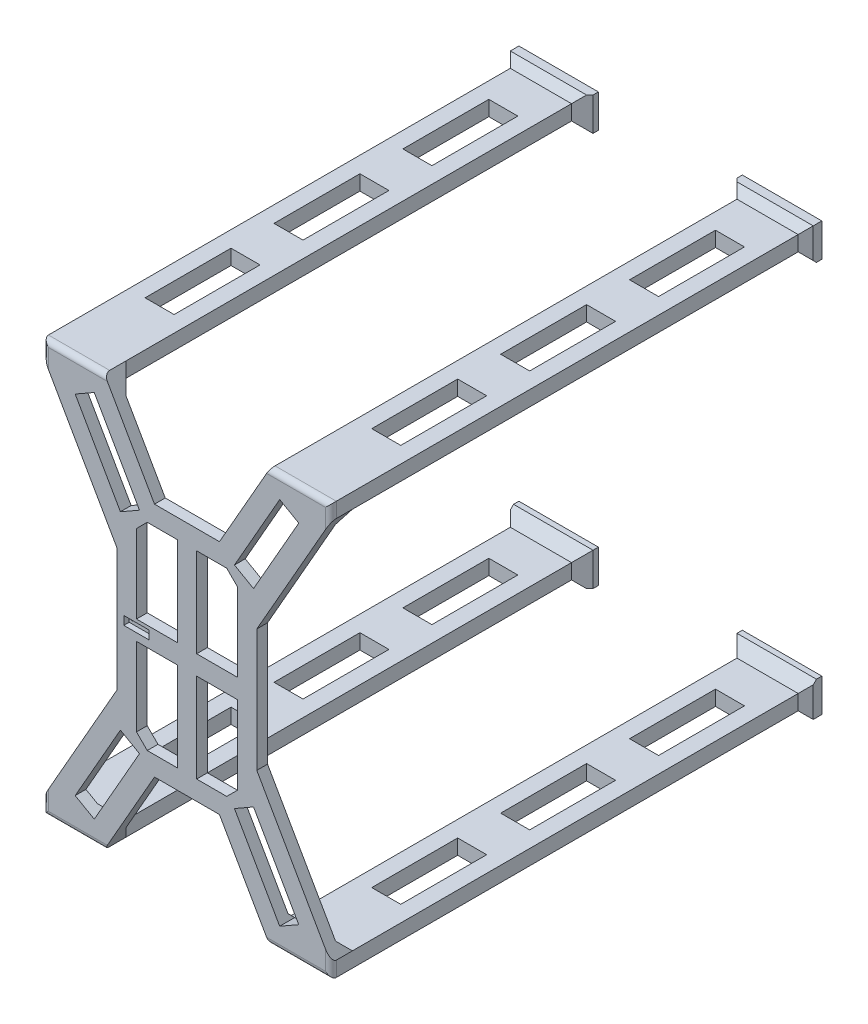
SolidWorks part; units mm, degrees
ref_plane "前视基准面" through (0, 0, 0) normal (0, 0, 1) x (1, 0, 0)
ref_plane "上视基准面" through (0, 0, 0) normal (0, 1, 0) x (1, 0, 0)
ref_plane "右视基准面" through (0, 0, 0) normal (1, 0, 0) x (0, 0, -1)
sketch "草图1" plane through (0, 0, 0) normal (0, 0, 1) x (1, 0, 0)
  line L0 (44, 200) -> (44, -200) construction
  line L1 (-325, -200) -> (325, -200) construction
  line L2 (-325, -200) -> (-325, 200) construction
  line L3 (-325, 200) -> (325, 200) construction
  line L4 (325, -200) -> (325, 200) construction
  line L5 (-325, -200) -> (325, 200) construction
  line L6 (-325, 200) -> (325, -200) construction
  line L7 (-290, 200) -> (-290, -200) construction
  line L8 (-325, 100) -> (325, 100) construction
  line L9 (-325, 0) -> (325, 0) construction
  line L10 (-325, -100) -> (325, -100) construction
  line L11 (-310, 200) -> (-310, -200) construction
  line L12 (-270, 200) -> (-270, -200) construction
  line L13 (24, 200) -> (24, -200) construction
  line L14 (64, 200) -> (64, -200) construction
  line L16 (-46, 192) -> (11, 192)
  line L17 (79, 0) -> (325, 0) construction
  line L18 (-46, 192) -> (-46, 178)
  line L19 (-46, 178) -> (11, 178)
  line L20 (11, 192) -> (11, 178)
  line L21 (-257, -178) -> (-200, -178)
  line L22 (-257, -178) -> (-257, -192)
  line L23 (325, 0) -> (225, 0) construction
  line L24 (-257, -192) -> (-200, -192)
  line L25 (-200, -178) -> (-200, -192)
  line L26 (-46, -178) -> (11, -178)
  line L27 (-46, -178) -> (-46, -192)
  line L28 (-46, -192) -> (11, -192)
  line L29 (11, -178) -> (11, -192)
  line L37 (-325, 185) -> (64, 185) construction
  line L38 (-325, -185) -> (64, -185) construction
  line L39 (-16, 200) -> (-16, 185) construction
  line L40 (4, 200) -> (4, 185) construction
  line L41 (-36, 200) -> (-36, 185) construction
  line L42 (-250, 200) -> (-250, 185) construction
  line L43 (-230, 200) -> (-230, 185) construction
  line L44 (-210, 200) -> (-210, 185) construction
  line L45 (-250, -200) -> (-250, -185) construction
  line L46 (-230, -200) -> (-230, -185) construction
  line L47 (-210, -200) -> (-210, -185) construction
  line L48 (4, -200) -> (4, -185) construction
  line L49 (-16, -200) -> (-16, -185) construction
  line L50 (-36, -200) -> (-36, -185) construction
  line L51 (64, -185) -> (325, -185) construction
  line L64 (-257, 192) -> (-200, 192)
  line L65 (-257, 192) -> (-257, 178)
  line L66 (-257, 178) -> (-200, 178)
  line L67 (-200, 192) -> (-200, 178)
  circle A0 centre (-310, 100) radius 3
  circle A1 centre (-290, 100) radius 3
  circle A2 centre (-270, 100) radius 3
  circle A3 centre (-310, 0) radius 3
  circle A4 centre (-290, 0) radius 3
  circle A5 centre (-270, 0) radius 3
  circle A6 centre (-310, -100) radius 3
  circle A7 centre (-290, -100) radius 3
  circle A8 centre (-270, -100) radius 3
  circle A9 centre (24, 100) radius 3
  circle A10 centre (44, 100) radius 3
  circle A11 centre (64, 100) radius 3
  circle A12 centre (24, -100) radius 3
  circle A13 centre (44, -100) radius 3
  circle A14 centre (64, -100) radius 3
  circle A15 centre (24, 0) radius 3
  circle A16 centre (44, 0) radius 3
  circle A17 centre (64, 0) radius 3
  circle A44 centre (-310, -185) radius 3
  circle A45 centre (-290, -185) radius 3
  circle A46 centre (-270, -185) radius 3
  circle A47 centre (24, -185) radius 3
  circle A48 centre (44, -185) radius 3
  circle A49 centre (64, -185) radius 3
  circle A50 centre (-310, 185) radius 3
  circle A51 centre (-290, 185) radius 3
  circle A52 centre (-270, 185) radius 3
  circle A53 centre (24, 185) radius 3
  circle A54 centre (44, 185) radius 3
  circle A55 centre (64, 185) radius 3
  circle A56 centre (-36, 185) radius 2
  circle A57 centre (-16, 185) radius 2
  circle A58 centre (4, 185) radius 2
  circle A59 centre (-250, 185) radius 2
  circle A60 centre (-230, 185) radius 2
  circle A61 centre (-210, 185) radius 2
  circle A62 centre (-250, -185) radius 2
  circle A63 centre (-230, -185) radius 2
  circle A64 centre (-210, -185) radius 2
  circle A65 centre (4, -185) radius 2
  circle A66 centre (-16, -185) radius 2
  circle A67 centre (-36, -185) radius 2
  point P0 (0, 0)
  dimension "D11" = 6
  dimension "D12" = 6
  dimension "D13" = 6
  dimension "D14" = 6
  dimension "D15" = 6
  dimension "D16" = 6
  dimension "D17" = 6
  dimension "D18" = 6
  dimension "D19" = 6
  dimension "D20" = 6
  dimension "D21" = 6
  dimension "D22" = 6
  dimension "D23" = 6
  dimension "D24" = 6
  dimension "D25" = 6
  dimension "D26" = 6
  dimension "D27" = 6
  dimension "D28" = 6
  dimension "D34" = 7
  dimension "D35" = 10
  dimension "D36" = 7
  dimension "D37" = 7
  dimension "D38" = 7
  dimension "D39" = 7
  dimension "D44" = 7
  dimension "D79" = 6
  dimension "D80" = 6
  dimension "D81" = 6
  dimension "D82" = 6
  dimension "D83" = 6
  dimension "D84" = 6
  dimension "D85" = 6
  dimension "D86" = 6
  dimension "D87" = 6
  dimension "D88" = 6
  dimension "D94" = 4
  dimension "D95" = 4
  dimension "D96" = 4
  dimension "D100" = 4
  dimension "D101" = 4
  dimension "D102" = 4
  dimension "D106" = 4
  dimension "D107" = 4
  dimension "D108" = 4
  dimension "D112" = 4
  dimension "D113" = 4
  dimension "D114" = 4
  dimension "D29" = 6
  dimension "D30" = 6
  dimension "D1" = 400
  dimension "D2" = 650
  dimension "D3" = 20
  dimension "D4" = 20
  dimension "D5" = 294
  dimension "D6" = 20
  dimension "D7" = 20
  dimension "D8" = 15
  dimension "D9" = 100
  dimension "D10" = 100
  dimension "D31" = 7
  dimension "D32" = 7
  dimension "D33" = 7
  dimension "D40" = 10
  dimension "D41" = 7
  dimension "D42" = 7
  dimension "D43" = 10
  dimension "D77" = 15
  dimension "D78" = 15
  dimension "D91" = 20
  dimension "D92" = 20
  dimension "D93" = 20
  dimension "D97" = 20
  dimension "D98" = 20
  dimension "D99" = 20
  dimension "D103" = 20
  dimension "D104" = 20
  dimension "D105" = 20
  dimension "D109" = 20
  dimension "D110" = 20
  dimension "D111" = 20
  dimension "D131" = 7
  dimension "D132" = 10
extrude "凸台-拉伸1" add sketch "草图1" along normal blind 440 contours L22 L21 L25 L24 | L27 L26 L29 L28 | L18 L16 L20 L19 | L65 L64 L67 L66
sketch "草图2" plane through (0, 0, 440) normal (0, 0, 1) x (1, 0, 0)
  line L0 (-257, 178) -> (-46, -192)
  line L1 (-200, 192) -> (11, -178)
  line L2 (-46, 192) -> (-257, -178)
  line L3 (-257, -178) -> (-257, -192) construction
  line L4 (-257, -178) -> (-200, -178) construction
  line L5 (11, 178) -> (-200, -192)
  line L6 (-257, 178) -> (-257, 192)
  line L7 (-257, 192) -> (-257, 178) construction
  line L8 (-257, 192) -> (-200, 192)
  line L9 (-46, 192) -> (11, 192)
  line L10 (11, 192) -> (11, 178)
  line L11 (-257, -178) -> (-257, -192)
  line L12 (-257, -192) -> (-200, -192)
  line L13 (-46, -192) -> (11, -192)
  line L14 (11, -192) -> (11, -178)
  line M2 (-200, -192) -> (-200, -178)
  line M3 (-200, -178) -> (-257, -178)
extrude "凸台-拉伸2" add sketch "草图2" along normal blind 10 contours L5 L0 L2 M3 M2 | L13 L14 L1 L5 L0 | L10 L9 L2 L1 L5 | L8 L6 L0 L2 L1 | L5 L1 L2 L0 | L12 L5 L10 L9 L2 L11 region at (-186.9015, 109.0049, 440) region at (-123, 0, 440) region at (-183.5044, -102.7988, 440) region at (-59.0985, -109.0049, 440) region at (-59.0985, 109.0049, 440)
sketch "草图4" plane through (0, 0, 0) normal (0, 0, -1) x (-1, 0, 0)
  line L0 (200, -185) -> (257, -185) construction
  line L1 (200, -178) -> (200, -192) construction
  line L2 (257, -178) -> (257, -192) construction
  line L5 (257, -192) -> (200, -192) construction
  line L6 (-11, -185) -> (46, -185) construction
  line L13 (211.5877, -182.25) -> (208.4123, -182.25)
  line L14 (208.4123, -182.25) -> (206.8246, -185)
  line L15 (206.8246, -185) -> (208.4123, -187.75)
  line L16 (208.4123, -187.75) -> (211.5877, -187.75)
  line L17 (211.5877, -187.75) -> (213.1754, -185)
  line L18 (213.1754, -185) -> (211.5877, -182.25)
  line L19 (251.5877, -182.25) -> (248.4123, -182.25)
  line L20 (248.4123, -182.25) -> (246.8246, -185)
  line L21 (246.8246, -185) -> (248.4123, -187.75)
  line L22 (248.4123, -187.75) -> (251.5877, -187.75)
  line L23 (251.5877, -187.75) -> (253.1754, -185)
  line L24 (253.1754, -185) -> (251.5877, -182.25)
  line L25 (-11, -178) -> (-11, -192) construction
  line L26 (46, -178) -> (46, -192) construction
  line L29 (46, -192) -> (-11, -192) construction
  line L30 (-11, 185) -> (46, 185) construction
  line L31 (-2.4123, -182.25) -> (-5.5877, -182.25)
  line L32 (-5.5877, -182.25) -> (-7.1754, -185)
  line L33 (-7.1754, -185) -> (-5.5877, -187.75)
  line L34 (-5.5877, -187.75) -> (-2.4123, -187.75)
  line L35 (-2.4123, -187.75) -> (-0.8246, -185)
  line L36 (-0.8246, -185) -> (-2.4123, -182.25)
  line L43 (37.5877, -187.75) -> (39.1754, -185)
  line L44 (39.1754, -185) -> (37.5877, -182.25)
  line L45 (37.5877, -182.25) -> (34.4123, -182.25)
  line L46 (34.4123, -182.25) -> (32.8246, -185)
  line L47 (32.8246, -185) -> (34.4123, -187.75)
  line L48 (34.4123, -187.75) -> (37.5877, -187.75)
  line L49 (-11, 192) -> (-11, 178) construction
  line L50 (46, 192) -> (46, 178) construction
  line L52 (46, 192) -> (-11, 192) construction
  line L55 (-2.4123, 187.75) -> (-5.5877, 187.75)
  line L56 (-5.5877, 187.75) -> (-7.1754, 185)
  line L57 (-7.1754, 185) -> (-5.5877, 182.25)
  line L58 (-5.5877, 182.25) -> (-2.4123, 182.25)
  line L59 (-2.4123, 182.25) -> (-0.8246, 185)
  line L60 (-0.8246, 185) -> (-2.4123, 187.75)
  line L67 (37.5877, 187.75) -> (34.4123, 187.75)
  line L68 (34.4123, 187.75) -> (32.8246, 185)
  line L69 (32.8246, 185) -> (34.4123, 182.25)
  line L70 (34.4123, 182.25) -> (37.5877, 182.25)
  line L71 (37.5877, 182.25) -> (39.1754, 185)
  line L72 (39.1754, 185) -> (37.5877, 187.75)
  line L73 (200, 185) -> (257, 185) construction
  line L74 (200, 192) -> (200, 178) construction
  line L75 (257, 192) -> (257, 178) construction
  line L77 (257, 192) -> (200, 192) construction
  line L79 (46, -178) -> (-11, -178) construction
  line L80 (211.5877, 187.75) -> (208.4123, 187.75)
  line L81 (208.4123, 187.75) -> (206.8246, 185)
  line L82 (206.8246, 185) -> (208.4123, 182.25)
  line L83 (208.4123, 182.25) -> (211.5877, 182.25)
  line L84 (211.5877, 182.25) -> (213.1754, 185)
  line L85 (213.1754, 185) -> (211.5877, 187.75)
  line L92 (251.5877, 187.75) -> (248.4123, 187.75)
  line L93 (248.4123, 187.75) -> (246.8246, 185)
  line L94 (246.8246, 185) -> (248.4123, 182.25)
  line L95 (248.4123, 182.25) -> (251.5877, 182.25)
  line L96 (251.5877, 182.25) -> (253.1754, 185)
  line L97 (253.1754, 185) -> (251.5877, 187.75)
  circle A1 centre (210, -185) radius 2.75 construction
  circle A2 centre (250, -185) radius 2.75 construction
  circle A3 centre (-4, -185) radius 2.75 construction
  circle A5 centre (36, -185) radius 2.75 construction
  circle A6 centre (-4, 185) radius 2.75 construction
  circle A8 centre (36, 185) radius 2.75 construction
  circle A9 centre (210, 185) radius 2.75 construction
  circle A10 centre (230, 185) radius 1.5
  circle A11 centre (250, 185) radius 2.75 construction
  circle A12 centre (16, 185) radius 1.5
  circle A13 centre (230, -185) radius 1.5
  circle A14 centre (16, -185) radius 1.5
  dimension "D14" = 20
  dimension "D19" = 3
  dimension "D4" = 7
  dimension "D9" = 20
  dimension "D11" = 3
  dimension "D25" = 3
  dimension "D26" = 3
  dimension "D3" = 5.5
  dimension "D5" = 5.5
  dimension "D6" = 7
  dimension "D7" = 20
  dimension "D8" = 5.5
  dimension "D10" = 5.5
  dimension "D12" = 7
  dimension "D13" = 5.5
  dimension "D15" = 5.5
  dimension "D16" = 7
  dimension "D17" = 20
  dimension "D18" = 5.5
  dimension "D20" = 5.5
  dimension "D21" = 20
  dimension "D22" = 20
  dimension "D23" = 20
  dimension "D24" = 20
extrude "切除-拉伸1" cut sketch "草图4" against normal blind 10
ref_plane "基准面1" through (-123, 0, 0) normal (-1, 0, 0) x (0, 0, 1)
ref_plane "基准面2" through (0, 0, 0) normal (0, -1, 0) x (-1, 0, 0)
sketch "草图6" plane through (0, 0, 440) normal (0, 0, -1) x (-1, 0, 0)
  line L0 (123, -204.7812) -> (123, 204.7812) construction
  line L1 (58, 110) -> (188, 110)
  line L2 (58, 110) -> (58, -110)
  line L3 (58, -110) -> (188, -110)
  line L4 (188, 110) -> (188, -110)
  line L5 (-145.6992, 0) -> (145.6992, 0) construction
  dimension "D1" = 65
  dimension "D2" = 65
  dimension "D3" = 110
  dimension "D4" = 110
extrude "凸台-拉伸3" add sketch "草图6" against normal up to surface (10 mm away) up to face at (-123, 0, 450)
sketch "草图7" plane through (0, 0, 450) normal (0, 0, 1) x (1, 0, 0)
  line L0 (-58, 57.0047) -> (-58, -57.0047) construction
  line L1 (-114, 9) -> (-76, 9)
  line L2 (-114, 9) -> (-114, 92)
  line L3 (-114, 92) -> (-76, 92)
  line L4 (-76, 9) -> (-76, 92)
  line L5 (-153.2378, 110) -> (-92.7622, 110) construction
  line L6 (-123, 204.7812) -> (-123, -204.7812) construction
  line L7 (-145.6992, 0) -> (145.6992, 0) construction
  line L8 (-92.7622, -110) -> (-153.2378, -110) construction
  line L9 (-114, -9) -> (-76, -9)
  line L10 (-114, -9) -> (-114, -92)
  line L11 (-114, -92) -> (-76, -92)
  line L12 (-76, -9) -> (-76, -92)
  line L13 (-132, 92) -> (-170, 92)
  line L14 (-132, 92) -> (-132, 9)
  line L15 (-132, 9) -> (-170, 9)
  line L16 (-170, 92) -> (-170, 9)
  line L17 (-132, -92) -> (-170, -92)
  line L18 (-132, -92) -> (-132, -9)
  line L19 (-132, -9) -> (-170, -9)
  line L20 (-170, -92) -> (-170, -9)
  line L21 (-188, -57.0047) -> (-188, 57.0047) construction
  line L22 (-227.0801, 161.8695) -> (-184.9728, 88.0321)
  line L23 (-184.9728, 88.0321) -> (-167.2085, 98.1625)
  line L24 (-167.2085, 98.1625) -> (-209.3158, 172)
  line L25 (-209.3158, 172) -> (-227.0801, 161.8695)
  line L26 (-257, 178) -> (-188, 57.0047) construction
  line L27 (-200, 192) -> (-153.2378, 110) construction
  line L28 (-78.7915, -98.1625) -> (-36.6842, -172)
  line L29 (-257, 192) -> (-200, 192) construction
  line L30 (-36.6842, 172) -> (-78.7915, 98.1625)
  line L31 (-78.7915, 98.1625) -> (-61.0272, 88.0321)
  line L32 (-61.0272, 88.0321) -> (-18.9199, 161.8695)
  line L33 (-18.9199, 161.8695) -> (-36.6842, 172)
  line L34 (11, 178) -> (-58, 57.0047) construction
  line L35 (-46, 192) -> (-92.7622, 110) construction
  line L36 (-46, 192) -> (11, 192) construction
  line L37 (-184.9728, -88.0321) -> (-227.0801, -161.8695)
  line L38 (-227.0801, -161.8695) -> (-209.3158, -172)
  line L39 (-209.3158, -172) -> (-167.2085, -98.1625)
  line L40 (-167.2085, -98.1625) -> (-184.9728, -88.0321)
  line L41 (-188, -57.0047) -> (-257, -178) construction
  line L42 (-153.2378, -110) -> (-200, -192) construction
  line L43 (-257, -192) -> (-200, -192) construction
  line L44 (-36.6842, -172) -> (-18.9199, -161.8695)
  line L45 (-18.9199, -161.8695) -> (-61.0272, -88.0321)
  line L46 (-61.0272, -88.0321) -> (-78.7915, -98.1625)
  line L47 (-58, -57.0047) -> (11, -178) construction
  line L48 (-92.7622, -110) -> (-46, -192) construction
  line L49 (-46, -192) -> (11, -192) construction
  dimension "D1" = 18
  dimension "D2" = 18
  dimension "D3" = 9
  dimension "D4" = 9
  dimension "D5" = 18
  dimension "D6" = 9
  dimension "D7" = 9
  dimension "D8" = 18
  dimension "D9" = 18
  dimension "D10" = 18
  dimension "D11" = 18
  dimension "D12" = 18
  dimension "D13" = 9
  dimension "D14" = 9
  dimension "D15" = 9
  dimension "D16" = 9
  dimension "D17" = 18
  dimension "D18" = 18
  dimension "D19" = 20
  dimension "D20" = 85
  dimension "D21" = 18
  dimension "D22" = 18
  dimension "D23" = 20
  dimension "D24" = 85
  dimension "D25" = 18
  dimension "D26" = 18
  dimension "D27" = 20
  dimension "D28" = 85
  dimension "D29" = 18
  dimension "D30" = 18
  dimension "D31" = 20
  dimension "D32" = 85
extrude "切除-拉伸2" cut sketch "草图7" against normal up to next (10 mm away)
sketch "草图8" plane through (0, -192, 0) normal (0, -1, 0) x (1, 0, 0)
  line L0 (-228.5, 0) -> (-228.5, 440) construction
  line L1 (-257, 0) -> (-200, 0) construction
  line L2 (-257, 440) -> (-200, 440) construction
  line L3 (-17.5, 0) -> (-17.5, 440) construction
  line L4 (-46, 0) -> (11, 0) construction
  line L5 (-257, 440) -> (-257, 0) construction
  line L6 (-242, 370) -> (-215, 370)
  line L7 (-242, 370) -> (-242, 290)
  line L8 (-242, 290) -> (-215, 290)
  line L9 (-215, 370) -> (-215, 290)
  line L10 (-242, 370) -> (-215, 290) construction
  line L11 (-242, 290) -> (-215, 370) construction
  line L12 (-242, 250) -> (-215, 250)
  line L13 (-242, 250) -> (-242, 170)
  line L14 (-242, 170) -> (-215, 170)
  line L15 (-215, 250) -> (-215, 170)
  line L16 (-242, 250) -> (-215, 170) construction
  line L17 (-242, 170) -> (-215, 250) construction
  line L18 (-242, 130) -> (-215, 130)
  line L19 (-242, 130) -> (-242, 50)
  line L20 (-242, 50) -> (-215, 50)
  line L21 (-215, 130) -> (-215, 50)
  line L22 (-242, 130) -> (-215, 50) construction
  line L23 (-242, 50) -> (-215, 130) construction
  line L24 (-46, 440) -> (-46, 0) construction
  line L25 (-31, 370) -> (-4, 370)
  line L26 (-31, 370) -> (-31, 290)
  line L27 (-31, 290) -> (-4, 290)
  line L28 (-4, 370) -> (-4, 290)
  line L29 (-31, 370) -> (-4, 290) construction
  line L30 (-31, 290) -> (-4, 370) construction
  line L31 (-31, 250) -> (-4, 250)
  line L32 (-31, 250) -> (-31, 170)
  line L33 (-31, 170) -> (-4, 170)
  line L34 (-4, 250) -> (-4, 170)
  line L35 (-31, 250) -> (-4, 170) construction
  line L36 (-31, 170) -> (-4, 250) construction
  line L37 (-31, 130) -> (-4, 130)
  line L38 (-31, 130) -> (-31, 50)
  line L39 (-31, 50) -> (-4, 50)
  line L40 (-4, 130) -> (-4, 50)
  line L41 (-31, 130) -> (-4, 50) construction
  line L42 (-31, 50) -> (-4, 130) construction
  point P10 (-228.5, 330)
  point P15 (-228.5, 210)
  point P20 (-228.5, 90)
  point P27 (-17.5, 330)
  point P32 (-17.5, 210)
  point P37 (-17.5, 90)
  dimension "D1" = 50
  dimension "D2" = 40
  dimension "D3" = 40
  dimension "D4" = 80
  dimension "D5" = 80
  dimension "D6" = 80
  dimension "D7" = 15
  dimension "D8" = 15
  dimension "D9" = 15
  dimension "D10" = 50
  dimension "D11" = 40
  dimension "D12" = 40
  dimension "D13" = 80
  dimension "D14" = 80
  dimension "D15" = 80
  dimension "D16" = 15
  dimension "D17" = 15
  dimension "D18" = 15
extrude "切除-拉伸3" cut sketch "草图8" against normal through all
sketch "草图9" plane through (0, 0, 440) normal (0, 0, -1) x (-1, 0, 0)
  line L0 (257, -192) -> (200, -192) construction
  line L1 (257, -178) -> (257, -192) construction
  line L2 (157.8424, 2) -> (181.5993, 2) construction
  circle A0 centre (170, 2) radius 1.5 construction
  circle A1 centre (161.175, 2) radius 1.5
  circle A2 centre (178.825, 2) radius 1.5
  dimension "D3" = 3
  dimension "D4" = 3
  dimension "D5" = 3
  dimension "D1" = 194
  dimension "D2" = 87
  dimension "D6" = 8.825
  dimension "D7" = 8.825
extrude "切除-拉伸4" cut sketch "草图9" against normal blind 10
sketch "草图10" plane through (0, 0, 450) normal (0, 0, 1) x (1, 0, 0)
  line L1 (-181.825, 6) -> (-158.175, 6)
  line L2 (-181.825, 6) -> (-181.825, -2)
  line L3 (-181.825, -2) -> (-158.175, -2)
  line L4 (-158.175, 6) -> (-158.175, -2)
  circle A0 centre (-178.825, 2) radius 1.5 construction
  circle A1 centre (-161.175, 2) radius 1.5 construction
  dimension "D1" = 4
  dimension "D2" = 4
  dimension "D3" = 3
  dimension "D4" = 3
extrude "切除-拉伸5" cut sketch "草图10" against normal blind 5
chamfer "倒角1" distance 10 angle 45 6 edges at (-46, -185, 440) (-17.5, -178, 440) (-46, 185, 440) (-17.5, 178, 440) (-200, 185, 440) (-228.5, 178, 440)
sketch "草图12" plane through (0, 0, 0) normal (0, 0, -1) x (-1, 0, 0)
  line L0 (46, 178) -> (56, 168) construction
  line L1 (-11, 192) -> (46, 192)
  line L2 (-11, 192) -> (-11, 178)
  line L3 (-11, 178) -> (46, 178)
  line L4 (46, 192) -> (46, 178)
  line L5 (46, 192) -> (46, 178) construction
  line L6 (46, -192) -> (-11, -192) construction
  line L7 (-21, 199) -> (56, 199)
  line L8 (-21, 199) -> (-21, 168)
  line L9 (-21, 168) -> (56, 168)
  line L10 (56, 199) -> (56, 168)
  line L11 (190, 199) -> (267, 199)
  line L12 (190, 199) -> (190, 168)
  line L13 (190, 168) -> (267, 168)
  line L14 (267, 199) -> (267, 168)
  line L15 (-21, -168) -> (56, -168)
  line L16 (-21, -168) -> (-21, -199)
  line L17 (-21, -199) -> (56, -199)
  line L18 (56, -168) -> (56, -199)
  line L19 (46, -178) -> (-11, -178) construction
  line L20 (-11, -178) -> (-11, -192) construction
  line L21 (46, -192) -> (46, -178) construction
  line L22 (257, 192) -> (200, 192) construction
  line L23 (-11, -178) -> (46, -178)
  line L24 (-11, -178) -> (-11, -192)
  line L25 (-11, -192) -> (46, -192)
  line L26 (46, -178) -> (46, -192)
  line L27 (200, 192) -> (257, 192)
  line L28 (200, 192) -> (200, 178)
  line L29 (200, 178) -> (257, 178)
  line L30 (257, 192) -> (257, 178)
  line L31 (200, 192) -> (200, 178) construction
  line L32 (257, -192) -> (200, -192) construction
  line L33 (200, -178) -> (257, -178)
  line L34 (200, -178) -> (200, -192)
  line L35 (200, -192) -> (257, -192)
  line L36 (257, -178) -> (257, -192)
  line L37 (257, -178) -> (257, -192) construction
  line L38 (190, -168) -> (267, -168)
  line L39 (190, -168) -> (190, -199)
  line L40 (190, -199) -> (267, -199)
  line L41 (267, -168) -> (267, -199)
  point P13 (46, 185)
  point P43 (267, 183.5)
  dimension "D1" = 7
  dimension "D2" = 10
  dimension "D3" = 10
  dimension "D4" = 10
  dimension "D5" = 7
  dimension "D6" = 10
  dimension "D7" = 10
  dimension "D8" = 10
  dimension "D9" = 7
  dimension "D10" = 10
  dimension "D11" = 10
  dimension "D12" = 10
  dimension "D13" = 10
  dimension "D14" = 7
  dimension "D15" = 10
  dimension "D16" = 10
extrude "凸台-拉伸4" add sketch "草图12" against normal blind 5
chamfer "倒角3" distance 10 angle 45 2 edges at (-200, -185, 440) (-228.5, -178, 440)
chamfer "倒角4" distance 10 angle 45 16 edges at (-46, -185, 5) (-17.5, -178, 5) (11, -185, 5) (-17.5, -192, 5) (-200, -185, 5) (-228.5, -192, 5) (-228.5, -178, 5) (-257, -185, 5) (-46, 185, 5) (-17.5, 192, 5) (-17.5, 178, 5) (11, 185, 5) (-200, 185, 5) (-228.5, 178, 5) (-257, 185, 5) (-228.5, 192, 5)
fillet "圆角1" radius 5 8 edges at (11, -185, 450) (-17.5, -192, 450) (-257, -185, 450) (-228.5, -192, 450) (-257, 185, 450) (-228.5, 192, 450) (11, 185, 450) (-17.5, 192, 450)
chamfer "倒角5" distance 10 angle 45 4 edges at (-170, 92, 445) (-76, 92, 445) (-170, -92, 445) (-76, -92, 445)
sketch "草图13" plane through (21, 0, 0) normal (1, 0, 0) x (0, 0, -1)
  line L1 (-38.6048, 219.5324) -> (29.6758, 219.5324)
  line L2 (-38.6048, 219.5324) -> (-38.6048, -229.6124)
  line L3 (-38.6048, -229.6124) -> (29.6758, -229.6124)
  line L4 (29.6758, 219.5324) -> (29.6758, -229.6124)
extrude "切除-拉伸6" cut sketch "草图13" against normal blind 3
sketch "草图14" plane through (-267, 0, 0) normal (-1, 0, 0) x (0, 0, 1)
  line L1 (-24.8814, 219.9753) -> (75.9121, 219.9753)
  line L2 (-24.8814, 219.9753) -> (-24.8814, -234.7568)
  line L3 (-24.8814, -234.7568) -> (75.9121, -234.7568)
  line L4 (75.9121, 219.9753) -> (75.9121, -234.7568)
extrude "切除-拉伸7" cut sketch "草图14" against normal blind 3
